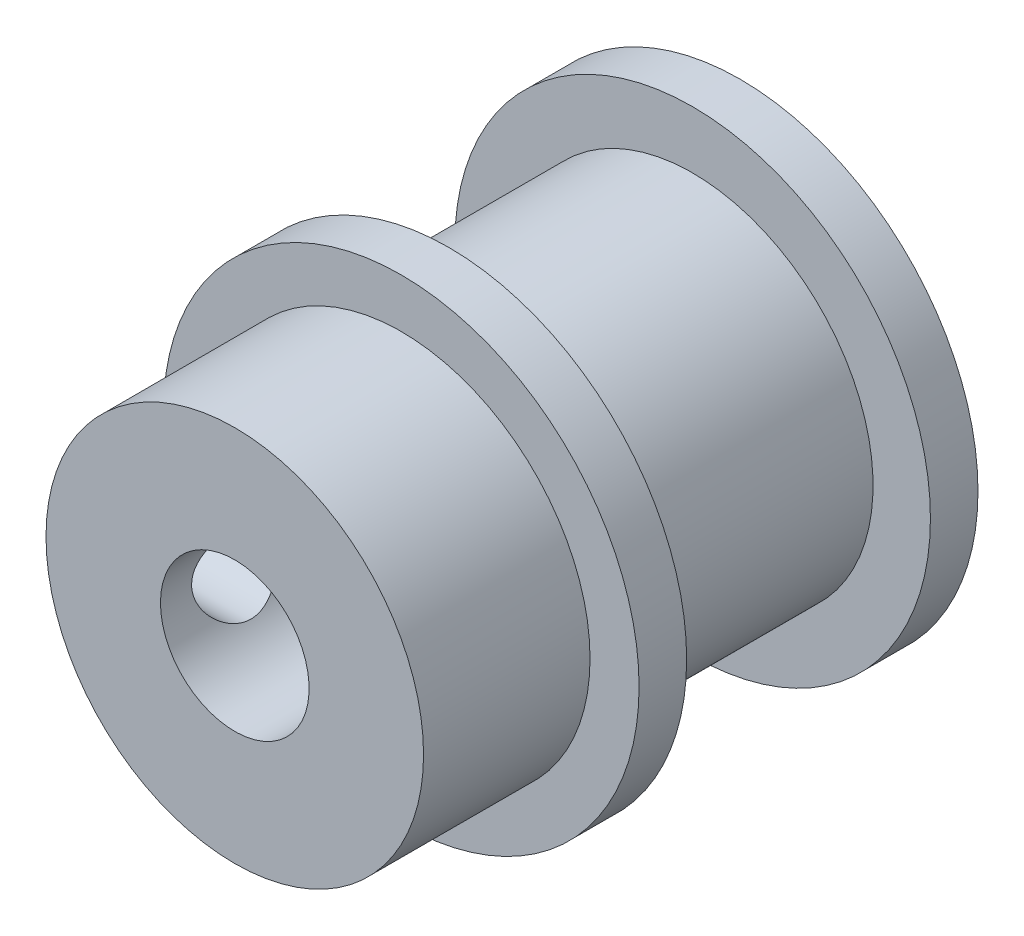
SolidWorks part; units mm, degrees
note: '?' marks a value the reader was unsure of.
ref_plane "Front Plane" through (0, 0, 0) normal (0, 0, 1) x (1, 0, 0)
ref_plane "Top Plane" through (0, 0, 0) normal (0, 1, 0) x (1, 0, 0)
ref_plane "Right Plane" through (0, 0, 0) normal (1, 0, 0) x (0, 0, -1)
ref_plane "Plane1" through (0, 0, 1.6) normal (0, 0, 1) x (1, 0, 0)
sketch "Sketch1" plane through (0, 0, 1.6) normal (0, 0, 1) x (1, 0, 0)
  circle A0 centre (0, 0) radius 8
extrude "Boss-Extrude1" add sketch "Sketch1" against normal blind 1.6
ref_plane "Plane2" through (0, 0, 9.8) normal (0, 0, 1) x (1, 0, 0)
sketch "Sketch2" plane through (0, 0, 9.8) normal (0, 0, 1) x (1, 0, 0)
  circle A0 centre (0, 0) radius 6.07
extrude "Boss-Extrude2" add sketch "Sketch2" against normal up to surface (8.2 mm away) up to face at (-8, 0, 1.6)
ref_plane "Plane3" through (0, 0, 9.8) normal (0, 0, -1) x (-1, 0, 0)
sketch "Sketch3" plane through (0, 0, 9.8) normal (0, 0, -1) x (-1, 0, 0)
  circle A0 centre (0, 0) radius 8
extrude "Boss-Extrude3" add sketch "Sketch3" against normal blind 1.6
ref_plane "Plane4" through (0, 0, 17) normal (0, 0, 1) x (1, 0, 0)
sketch "Sketch4" plane through (0, 0, 17) normal (0, 0, 1) x (1, 0, 0)
  circle A0 centre (0, 0) radius 6.35
extrude "Boss-Extrude4" add sketch "Sketch4" against normal up to surface (5.6 mm away) up to face at (8, 0, 11.4)
hole_wizard "Ø5.0 (5) Diameter Hole1" positions "Sketch6" profile "Sketch5" hole size "Ø5.0" standard "ANSI Metric"
sketch "Sketch6" plane through (0, 0, 0) normal (0, 0, -1) x (-1, 0, 0)
  point P0 (0, 0)
sketch "Sketch5" plane through (0, 0, 0) normal (1, 0, 0) x (0, 1, 0)
  line L0 (0, 0) -> (0, 17)
  line L1 (0, 17) -> (2.5, 17)
  line L2 (2.5, 17) -> (2.5, 0)
  line L5 (2.5, 0) -> (0, 0)
  line L11 (0, -6.35) -> (0, 107.95) construction
  dimension "Thru Hole Dia." = 5
  dimension "Thru Hole Depth" = 17
hole_wizard "Ø3.0 (3) Diameter Hole1" positions "3DSketch1" profile "Sketch7" hole size "Ø3.0" standard "ANSI Metric"
sketch3d "3DSketch1"
  point P0 (-6.35, 0, 14.4528)
sketch "Sketch7" plane through (-6.35, 0, 14.4528) normal (0, 1, 0) x (0, 0, 1)
  line L0 (0, 0) -> (0, 3.85)
  line L1 (0, 3.85) -> (1.5, 3.85)
  line L2 (1.5, 3.85) -> (1.5, 0)
  line L5 (1.5, 0) -> (0, 0)
  line L11 (0, -6.35) -> (0, 107.95) construction
  dimension "Thru Hole Dia." = 3
  dimension "Thru Hole Depth" = 3.85
ref_axis "Axis1" through (0, 0, 17) along (0, 0, -1)?
ref_plane "Plane5" through (0, 0, 5.7) normal (0, 0, 1) x (1, 0, 0)
